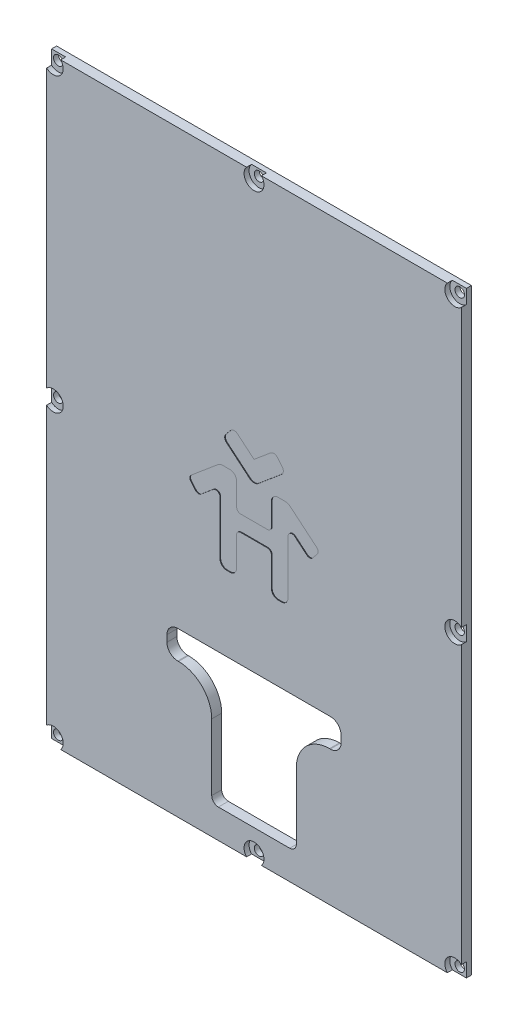
SolidWorks part; units mm, degrees
ref_plane "Спереди" through (0, 0, 0) normal (0, 0, 1) x (1, 0, 0)
ref_plane "Сверху" through (0, 0, 0) normal (0, 1, 0) x (1, 0, 0)
ref_plane "Справа" through (0, 0, 0) normal (1, 0, 0) x (0, 0, -1)
sketch "Эскиз1" plane through (0, 0, 0) normal (0, 0, 1) x (1, 0, 0)
  line L1 (-62.5, -90) -> (62.5, -90)
  line L2 (-62.5, -90) -> (-62.5, 90)
  line L3 (-62.5, 90) -> (62.5, 90)
  line L4 (62.5, -90) -> (62.5, 90)
  line L5 (-62.5, -90) -> (62.5, 90) construction
  line L6 (-62.5, 90) -> (62.5, -90) construction
  point P0 (0, 0)
  dimension "D1" = 125
  dimension "D2" = 180
extrude "Бобышка-Вытянуть1" add sketch "Эскиз1" along normal blind 3
sketch "Эскиз2" plane through (0, 0, 0) normal (0, 0, -1) x (-1, 0, 0)
  line L0 (-26.25, -44) -> (-26.25, -46)
  line L1 (-23, -49.25) -> (-22.75, -49.25)
  line L2 (-12.75, -59.25) -> (-12.75, -79.25)
  line L3 (-10.75, -81.25) -> (10.75, -81.25)
  line L4 (12.75, -79.25) -> (12.75, -59.25)
  line L5 (22.75, -49.25) -> (23, -49.25)
  line L6 (26.25, -46) -> (26.25, -44)
  line L7 (23, -40.75) -> (-23, -40.75)
  line L8 (-62.5, -90) -> (-62.5, 90) construction
  line L9 (62.5, 90) -> (62.5, -90) construction
  line L10 (62.5, -90) -> (-62.5, -90) construction
  arc A0 (22.75, -49.25) -> (12.75, -59.25) centre (22.75, -59.25) ccw
  arc A1 (-12.75, -59.25) -> (-22.75, -49.25) centre (-22.75, -59.25) ccw
  arc A2 (23, -49.25) -> (26.25, -46) centre (23, -46) ccw
  arc A3 (26.25, -44) -> (23, -40.75) centre (23, -44) ccw
  arc A4 (-23, -49.25) -> (-26.25, -46) centre (-23, -46) cw
  arc A5 (-23, -40.75) -> (-26.25, -44) centre (-23, -44) ccw
  arc A6 (12.75, -79.25) -> (10.75, -81.25) centre (10.75, -79.25) cw
  arc A7 (-10.75, -81.25) -> (-12.75, -79.25) centre (-10.75, -79.25) cw
  point P16 (12.75, -49.25)
  point P21 (26.25, -49.25)
  point P24 (26.25, -40.75)
  point P31 (12.75, -81.25)
  point P34 (-12.75, -81.25)
  dimension "D7" = 10
  dimension "D8" = 3.25
  dimension "D9" = 2
  dimension "D1" = 36.25
  dimension "D2" = 36.25
  dimension "D3" = 49.25
  dimension "D4" = 8.5
  dimension "D5" = 25.5
  dimension "D6" = 32
extrude "Вырез-Вытянуть1" cut sketch "Эскиз2" against normal blind 10
sketch "Эскиз3" plane through (0, 0, 3) normal (0, 0, 1) x (1, 0, 0)
  line L0 (-60.5, -940.9285) -> (-60.5, 49059.0715) construction
  line L1 (60.5, -944.6511) -> (60.5, 49055.3489) construction
  line L2 (-1032.3277, 88) -> (48967.6723, 88) construction
  line L3 (-1028.801, -88) -> (48971.199, -88) construction
  line L4 (-62.5, -90) -> (62.5, -90) construction
  line L6 (-62.5, 90) -> (-62.5, -90) construction
  line L7 (62.5, -90) -> (62.5, 90) construction
  line L8 (62.5, 90) -> (-62.5, 90) construction
  line L9 (0, -925) -> (0, 49075) construction
  line L10 (-1052.5, 0) -> (48947.5, 0) construction
  circle A0 centre (-60.5, 88) radius 3
  circle A1 centre (0, 88) radius 3
  circle A2 centre (60.5, 88) radius 3
  circle A3 centre (60.5, 0) radius 3
  circle A4 centre (60.5, -88) radius 3
  circle A5 centre (0, -88) radius 3
  circle A6 centre (-60.5, -88) radius 3
  circle A7 centre (-60.5, 0) radius 3
  point P19 (0, 90)
  point P22 (-62.5, 0)
  dimension "D5" = 6
  dimension "D1" = 2
  dimension "D2" = 2
  dimension "D3" = 2
  dimension "D4" = 2
extrude "Вырез-Вытянуть2" cut sketch "Эскиз3" against normal blind 1.5
sketch "Эскиз4" plane through (0, 0, 1.5) normal (0, 0, 1) x (1, 0, 0)
  circle A0 centre (-60.5, 88) radius 1.425
  circle A1 centre (0, 88) radius 1.425
  circle A2 centre (60.5, 88) radius 1.425
  circle A3 centre (60.5, 0) radius 1.425
  circle A4 centre (60.5, -88) radius 1.425
  circle A5 centre (0, -88) radius 1.425
  circle A6 centre (-60.5, -88) radius 1.425
  circle A7 centre (-60.5, 0) radius 1.425
  dimension "D1" = 2.85
extrude "Вырез-Вытянуть3" cut sketch "Эскиз4" against normal blind 2
sketch "Эскиз5" plane through (0, 0, 3) normal (0, 0, 1) x (1, 0, 0)
  line L0 (-10.25, -0.0911) -> (-10.25, -16.2185)
  line L1 (-8.25, -18.2185) -> (-7.25, -18.2185)
  line L2 (-5.25, -16.2185) -> (-5.25, -7.4685)
  line L3 (-4, -6.2185) -> (4, -6.2185)
  line L4 (-9.3401, 8.5815) -> (-7.25, 8.5815)
  line L5 (-5.25, 6.5815) -> (-5.25, -0.1685)
  line L6 (0, -1000.6685) -> (0, 48999.3315) construction
  line L7 (-4, -1.4185) -> (4, -1.4185)
  line L8 (-10.947, 7.9966) -> (-18.868, 1.3501)
  line L9 (-19.0221, -0.4109) -> (-17.6786, -2.012)
  line L10 (-15.9176, -2.1661) -> (-12.3035, 0.8665)
  line L11 (15.9176, -2.1661) -> (12.3035, 0.8665)
  line L12 (19.0221, -0.4109) -> (17.6786, -2.012)
  line L13 (10.947, 7.9966) -> (18.868, 1.3501)
  line L14 (5.25, 6.5815) -> (5.25, -0.1685)
  line L15 (9.3401, 8.5815) -> (7.25, 8.5815)
  line L16 (5.25, -16.2185) -> (5.25, -7.4685)
  line L17 (8.25, -18.2185) -> (7.25, -18.2185)
  line L18 (10.25, -0.0911) -> (10.25, -16.2185)
  line L19 (0, 14.8585) -> (-4.9795, 19.0368)
  line L20 (-7.0927, 18.8519) -> (-8.4839, 17.194)
  line L21 (-8.299, 15.0808) -> (-1.2856, 9.1958)
  line L22 (8.299, 15.0808) -> (1.2856, 9.1958)
  line L23 (0, 14.8585) -> (4.9795, 19.0368)
  line L24 (7.0927, 18.8519) -> (8.4839, 17.194)
  arc A0 (-10.25, -16.2185) -> (-8.25, -18.2185) centre (-8.25, -16.2185) ccw
  arc A1 (-7.25, -18.2185) -> (-5.25, -16.2185) centre (-7.25, -16.2185) ccw
  arc A2 (-5.25, 6.5815) -> (-7.25, 8.5815) centre (-7.25, 6.5815) ccw
  arc A3 (-9.3401, 8.5815) -> (-10.947, 7.9966) centre (-9.3401, 6.0815) ccw
  arc A4 (-4, -6.2185) -> (-5.25, -7.4685) centre (-4, -7.4685) ccw
  arc A5 (-4, -1.4185) -> (-5.25, -0.1685) centre (-4, -0.1685) cw
  arc A6 (-10.25, -0.0911) -> (-12.3035, 0.8665) centre (-11.5, -0.0911) ccw
  arc A7 (-15.9176, -2.1661) -> (-17.6786, -2.012) centre (-16.721, -1.2085) cw
  arc A8 (-18.868, 1.3501) -> (-19.0221, -0.4109) centre (-18.0645, 0.3926) ccw
  arc A9 (18.868, 1.3501) -> (19.0221, -0.4109) centre (18.0645, 0.3926) cw
  arc A10 (15.9176, -2.1661) -> (17.6786, -2.012) centre (16.721, -1.2085) ccw
  arc A11 (10.25, -0.0911) -> (12.3035, 0.8665) centre (11.5, -0.0911) cw
  arc A12 (4, -1.4185) -> (5.25, -0.1685) centre (4, -0.1685) ccw
  arc A13 (4, -6.2185) -> (5.25, -7.4685) centre (4, -7.4685) cw
  arc A14 (9.3401, 8.5815) -> (10.947, 7.9966) centre (9.3401, 6.0815) cw
  arc A15 (5.25, 6.5815) -> (7.25, 8.5815) centre (7.25, 6.5815) cw
  arc A16 (7.25, -18.2185) -> (5.25, -16.2185) centre (7.25, -16.2185) cw
  arc A17 (10.25, -16.2185) -> (8.25, -18.2185) centre (8.25, -16.2185) cw
  arc A18 (-8.299, 15.0808) -> (-8.4839, 17.194) centre (-7.3348, 16.2298) cw
  arc A19 (-4.9795, 19.0368) -> (-7.0927, 18.8519) centre (-5.9437, 17.8877) ccw
  arc A20 (4.9795, 19.0368) -> (7.0927, 18.8519) centre (5.9437, 17.8877) cw
  arc A21 (8.299, 15.0808) -> (8.4839, 17.194) centre (7.3348, 16.2298) ccw
  arc A22 (1.2856, 9.1958) -> (-1.2856, 9.1958) centre (0, 10.7279) cw
  point P35 (0, -6.2185)
  point P36 (0, -1.4185)
  point P61 (19.57, 0.5466)
  point P62 (4.9945, -1.4185)
  point P63 (4.9945, -6.2185)
  point P64 (9.9945, 8.5815)
  point P65 (4.9945, 8.5815)
  point P66 (4.9945, -18.2185)
  point P67 (9.9945, -18.2185)
  point P79 (5.7231, 19.8752)
  point P80 (8.937, 16.0449)
  dimension "D3" = 2
  dimension "D4" = 2.5
  dimension "D6" = 1.5
  dimension "D7" = 2
  dimension "D8" = 1.25
  dimension "D1" = 5.25
  dimension "D2" = 50
  dimension "D5" = 50
extrude "Вырез-Вытянуть4" cut sketch "Эскиз5" against normal blind 0.2
